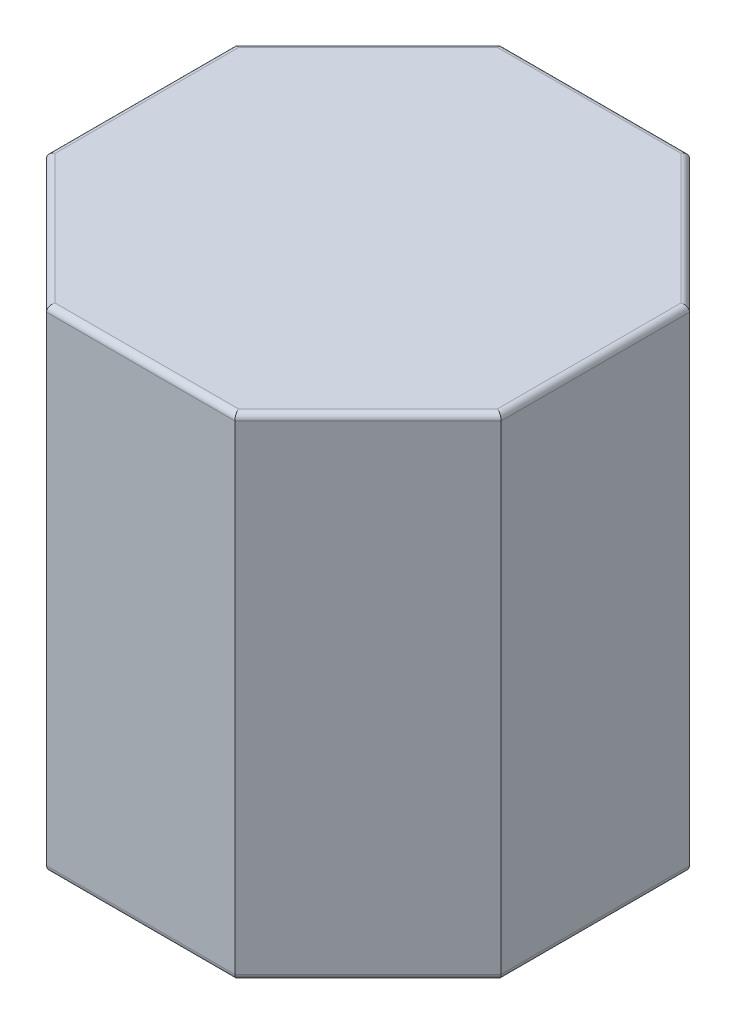
SolidWorks part; units mm, degrees
ref_plane "Front Plane" through (0, 0, 0) normal (0, 0, 1) x (1, 0, 0)
ref_plane "Top Plane" through (0, 0, 0) normal (0, 1, 0) x (1, 0, 0)
ref_plane "Right Plane" through (0, 0, 0) normal (1, 0, 0) x (0, 0, -1)
sketch "Sketch1" plane through (0, 0, 0) normal (0, 1, 0) x (1, 0, 0)
  line L0 (0, 0) -> (32.5178, 0) construction
  line L1 (-7.663, 18.5) -> (-18.5, 7.663)
  line L2 (-18.5, 7.663) -> (-18.5, -7.663)
  line L3 (-18.5, -7.663) -> (-7.663, -18.5)
  line L4 (-7.663, -18.5) -> (7.663, -18.5)
  line L5 (7.663, -18.5) -> (18.5, -7.663)
  line L6 (18.5, -7.663) -> (18.5, 7.663)
  line L7 (18.5, 7.663) -> (7.663, 18.5)
  line L8 (7.663, 18.5) -> (-7.663, 18.5)
  circle A0 centre (0, 0) radius 18.5 construction
  dimension "D1" = 37
extrude "Boss-Extrude1" add sketch "Sketch1" along normal blind 40
fillet "Fillet1" radius 0.5 16 edges at (-13.0815, 0, -13.0815) (-18.5, 0, 0) (-13.0815, 0, 13.0815) (0, 0, 18.5) (13.0815, 0, 13.0815) (18.5, 0, 0) (13.0815, 0, -13.0815) (0, 0, -18.5) (13.0815, 40, -13.0815) (18.5, 40, 0) (13.0815, 40, 13.0815) (0, 40, 18.5) (-13.0815, 40, 13.0815) (-18.5, 40, 0) (-13.0815, 40, -13.0815) (0, 40, -18.5)
